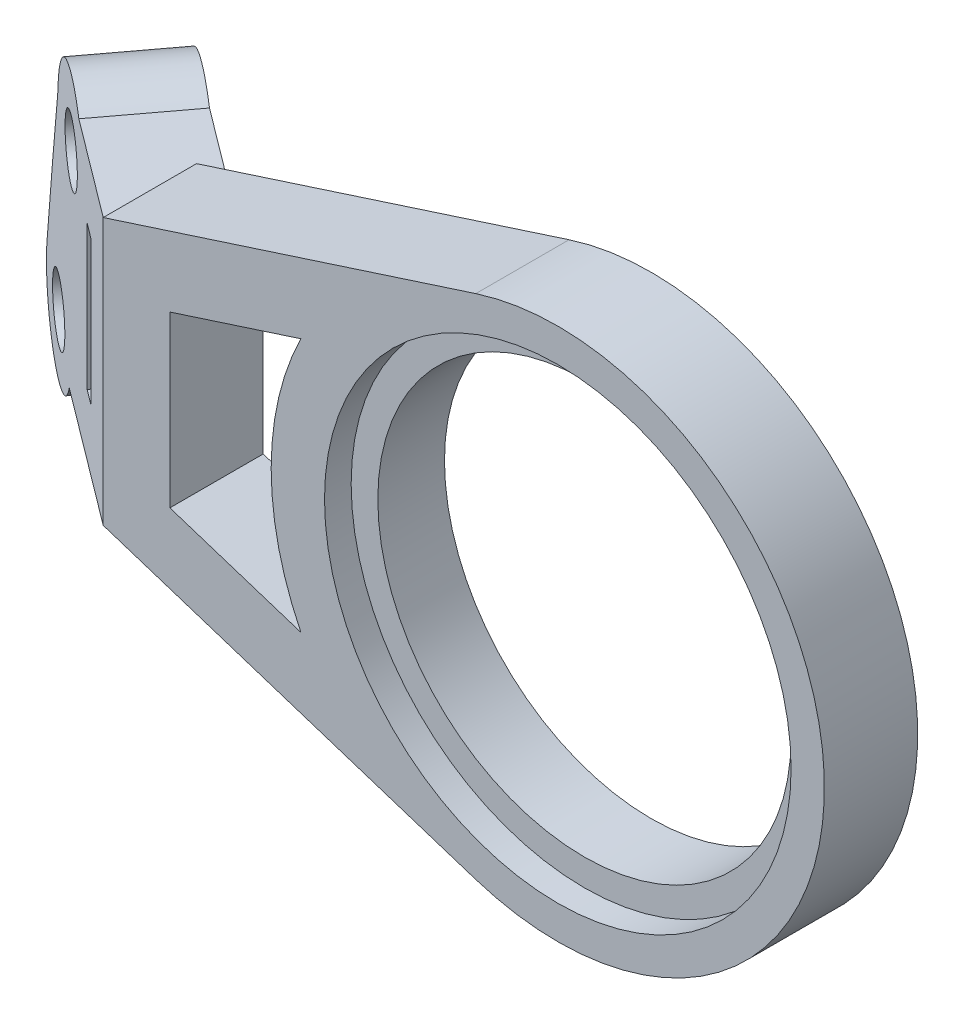
SolidWorks part; units mm, degrees
ref_plane "Front Plane" through (0, 0, 0) normal (0, 0, 1) x (1, 0, 0)
ref_plane "Top Plane" through (0, 0, 0) normal (0, 1, 0) x (1, 0, 0)
ref_plane "Right Plane" through (0, 0, 0) normal (1, 0, 0) x (0, 0, -1)
sketch "草图1" plane through (0, 0, 0) normal (0, 0, 1) x (1, 0, 0)
  line L0 (-3.0748, 9.5155) -> (-17.0488, 5)
  line L5 (-3.0748, -9.5155) -> (-17.0488, -5)
  line L11 (-17.0488, 5) -> (-17.0488, -5)
  line L12 (-14.5488, 3.1806) -> (-14.5488, -3.1806)
  line L13 (-14.5488, -3.1806) -> (-9.6345, -4.7686)
  line L15 (-9.6345, 4.7686) -> (-14.5488, 3.1806)
  circle A0 centre (0, 0) radius 7.75
  arc A10 (-3.0748, 9.5155) -> (-3.0748, -9.5155) centre (0, 0) cw
  arc A11 (-9.6345, 4.7686) -> (-9.6345, -4.7686) centre (0, 0) ccw
  dimension "D3" = 15.5
  dimension "D4" = 2.5
  dimension "D7" = 10
  dimension "D1" = 10
  dimension "D6" = 3
  dimension "D2" = 2.5
  dimension "D5" = 2.5
extrude "凸台-拉伸1" add sketch "草图1" along normal blind 3.5
sketch "草图2" plane through (0, 0, 3.5) normal (0, 0, 1) x (1, 0, 0)
  circle A0 centre (0, 0) radius 8.75
  dimension "D1" = 17.5
extrude "切除-拉伸1" cut sketch "草图2" against normal blind 1
sketch "草图3" plane through (0, 0, 0) normal (0, 1, 0) x (1, 0, 0)
  line L0 (-17.0488, -3.5) -> (-24.6632, 2.2148)
  line L4 (-15.8814, 0) -> (-22.5623, 5.0141)
  line L5 (-3.0748, 0) -> (-17.0488, 0) construction
  line L6 (-22.5623, 5.0141) -> (-24.6632, 2.2148)
  line L7 (-15.8814, 0) -> (-17.0488, -3.5)
  dimension "D1" = 3.5
extrude "凸台-拉伸2" add sketch "草图3" along normal mid plane 10
sketch "草图4" plane through (-7.8234, 0, 10.4239) normal (-0.6003, 0, 0.7998) x (0.7998, 0, 0.6003)
  line L0 (-21.0551, 5) -> (-21.0551, -5) construction
  line L1 (-21.0551, -5) -> (-11.5347, -5) construction
  line L2 (-21.0551, 5) -> (-11.5347, 5) construction
  line L4 (-19.9399, 3.7057) -> (-22.0991, -3.16)
  line L5 (-17.9132, -5) -> (-17.3488, 1.2412)
  line L6 (-17.3488, 1.2412) -> (-16.116, 2.2695)
  line L7 (-16.116, 2.2695) -> (-16.116, 5)
  circle A0 centre (-17.5551, 2.9557) radius 1.15
  circle A1 centre (-19.9051, -3.85) radius 1.15
  arc A2 (-17.9132, -5) -> (-22.0991, -3.16) centre (-19.9051, -3.85) cw
  arc A3 (-16.116, 5) -> (-19.9399, 3.7057) centre (-17.5551, 2.9557) ccw
  dimension "D1" = 2.3
  dimension "D2" = 2.3
  dimension "D5" = 2.5
  dimension "D6" = 2.3
  dimension "D3" = 7.2
  dimension "D4" = 3.5
sketch "草图8" plane through (-7.8234, 0, 10.4239) normal (-0.6003, 0, 0.7998) x (0.7998, 0, 0.6003)
  line L0 (-21.0551, 5) -> (-11.5347, 5) construction
  line L1 (-14.5551, 2.7) -> (-13.8347, 2.7)
  line L2 (-14.5551, 2.7) -> (-14.5551, -2.7)
  line L3 (-14.5551, -2.7) -> (-13.8347, -2.7)
  line L4 (-13.8347, 2.7) -> (-13.8347, -2.7)
  line L5 (-14.5551, 2.7) -> (-13.8347, -2.7) construction
  line L6 (-14.5551, -2.7) -> (-13.8347, 2.7) construction
  line L7 (-21.0551, -5) -> (-11.5347, -5) construction
  line L8 (-11.5347, 5) -> (-11.5347, -5) construction
  circle A0 centre (-17.5551, 2.9557) radius 1.15 construction
  point P4 (-14.1949, 0)
  dimension "D1" = 2.3
  dimension "D2" = 2.3
  dimension "D3" = 2.3
  dimension "D4" = 3
extrude "切除-拉伸6" cut sketch "草图8" against normal through all
extrude "凸台-拉伸6" add sketch "草图4" against normal blind 3.5 contours A2 L4 A3 L7 L6 L5
extrude "切除-拉伸9" cut sketch "草图4<9>" against normal through all contours A1 | A0
sketch "草图4<9>" plane through (-7.8234, 0, 10.4239) normal (-0.6003, 0, 0.7998) x (0.7998, 0, 0.6003) same geometry as "草图4"
sketch "草图9" plane through (-7.8234, 0, 10.4239) normal (-0.6003, 0, 0.7998) x (0.7998, 0, 0.6003)
  line L0 (-21.0551, 0.1598) -> (-20.0468, 3.1593)
  line L1 (-18.9941, 5) -> (-18.9941, 5.4718)
  line L2 (-18.9941, 5.4718) -> (-21.9063, 5.4718)
  line L3 (-21.9063, 5.4718) -> (-21.9063, 0.1598)
  line L5 (-21.9063, 0.1598) -> (-21.0551, 0.1598)
  arc A0 (-18.9941, 5) -> (-20.0468, 3.1593) centre (-17.5551, 2.9557) ccw
extrude "切除-拉伸10" cut sketch "草图9" against normal blind 3.5
